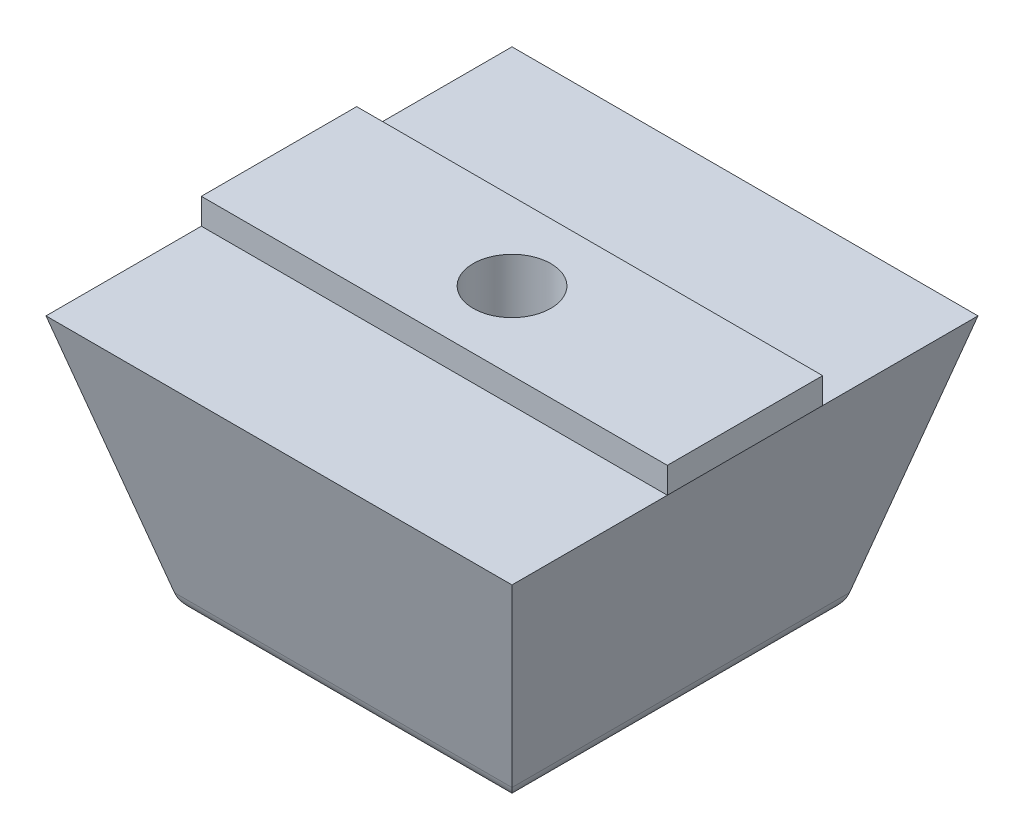
SolidWorks part; units mm, degrees
ref_plane "Front Plane" through (0, 0, 0) normal (0, 0, 1) x (1, 0, 0)
ref_plane "Top Plane" through (0, 0, 0) normal (0, 1, 0) x (1, 0, 0)
ref_plane "Right Plane" through (0, 0, 0) normal (1, 0, 0) x (0, 0, -1)
sketch "Sketch1" plane through (0, 0, 0) normal (0, 1, 0) x (1, 0, 0)
  line L1 (-9, -9) -> (9, -9)
  line L2 (-9, -9) -> (-9, 9)
  line L3 (-9, 9) -> (9, 9)
  line L4 (9, -9) -> (9, 9)
  line L5 (-9, -9) -> (9, 9) construction
  line L6 (-9, 9) -> (9, -9) construction
  point P0 (0, 0)
  dimension "D1" = 18
  dimension "D2" = 18
extrude "Boss-Extrude1" add sketch "Sketch1" against normal blind 10 draft 15
sketch "Sketch5" plane through (0, 0, 0) normal (0, 1, 0) x (1, 0, 0)
  line L0 (9, -9) -> (9, 9) construction
  line L1 (-9, -3) -> (9, -3)
  line L2 (-9, -3) -> (-9, 3)
  line L3 (-9, 3) -> (9, 3)
  line L4 (9, -3) -> (9, 3)
  line L5 (-9, -3) -> (9, 3) construction
  line L6 (-9, 3) -> (9, -3) construction
  point P0 (0, 0)
  dimension "D1" = 6
extrude "Boss-Extrude3" add sketch "Sketch5" along normal blind 3
fillet "Fillet2" radius 1 2 edges at (0, 3, 3) (0, 3, -3)
sketch "Sketch6" plane through (0, 3, 0) normal (0, 1, 0) x (1, 0, 0)
  circle A0 centre (0, 0) radius 1.5
  dimension "D1" = 3
extrude "Cut-Extrude3" cut sketch "Sketch6" against normal up to next
sketch "Sketch7" plane through (0, -10, 0) normal (0, -1, 0) x (1, 0, 0)
  circle A0 centre (0, 0) radius 2.875
  dimension "D1" = 5.75
extrude "Cut-Extrude4" cut sketch "Sketch7" against normal offset from surface (8 mm away) 2 up to face at (-2.25, 0, 6)
sketch "Sketch9" plane through (0, 3, 0) normal (0, 1, 0) x (1, 0, 0)
  line L0 (9, 3) -> (-9, 3) construction
  line L1 (-10, -3) -> (10, -3)
  line L2 (-10, -3) -> (-10, 3)
  line L3 (-10, 3) -> (10, 3)
  line L4 (10, -3) -> (10, 3)
  line L5 (-10, -3) -> (10, 3) construction
  line L6 (-10, 3) -> (10, -3) construction
  point P0 (0, 0)
  dimension "D1" = 20
extrude "Cut-Extrude5" cut sketch "Sketch9" against normal blind 2
fillet "Fillet4" radius 1 4 edges at (6.3205, -10, 0) (0, -10, -6.3205) (-6.3205, -10, 0) (0, -10, 6.3205)
